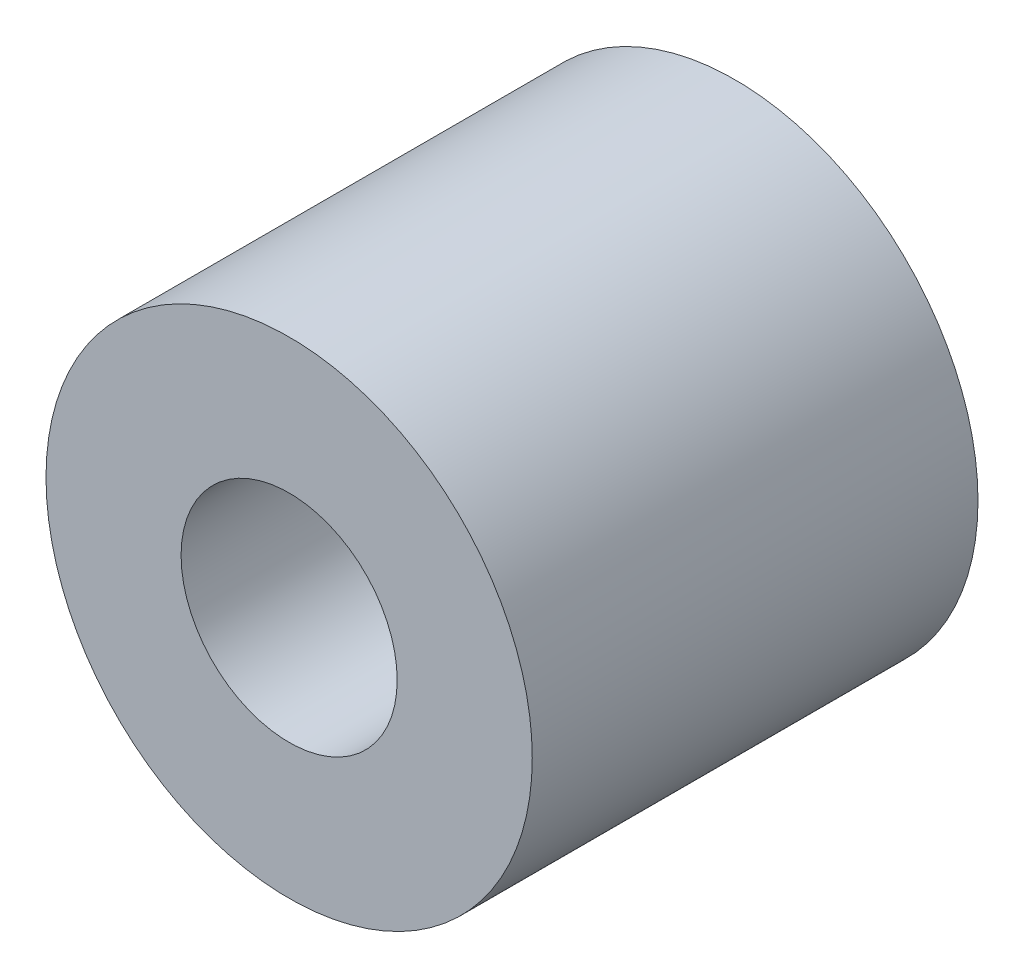
SolidWorks part; units mm, degrees
ref_plane "Ebene vorne" through (0, 0, 0) normal (1, 0, 0) x (0, 1, 0)
ref_plane "Ebene oben" through (0, 0, 0) normal (0, 0, 1) x (0, 1, 0)
ref_plane "Ebene rechts" through (0, 0, 0) normal (0, 1, 0) x (-1, 0, 0)
sketch "Skizze1" plane through (0, 0, 0) normal (0, 0, 1) x (0, 1, 0)
  circle A0 centre (0, 0) radius 9
  dimension "D1" = 18
extrude "Aufsatz-Linear austragen1" add sketch "Skizze1" along normal blind 16.5
sketch "Skizze2" plane through (0, 0, 16.5) normal (0, 0, 1) x (1, 0, 0)
  circle A0 centre (0, 0) radius 4
  dimension "D1" = 8
extrude "Schnitt-Linear austragen1" cut sketch "Skizze2" against normal up to next
